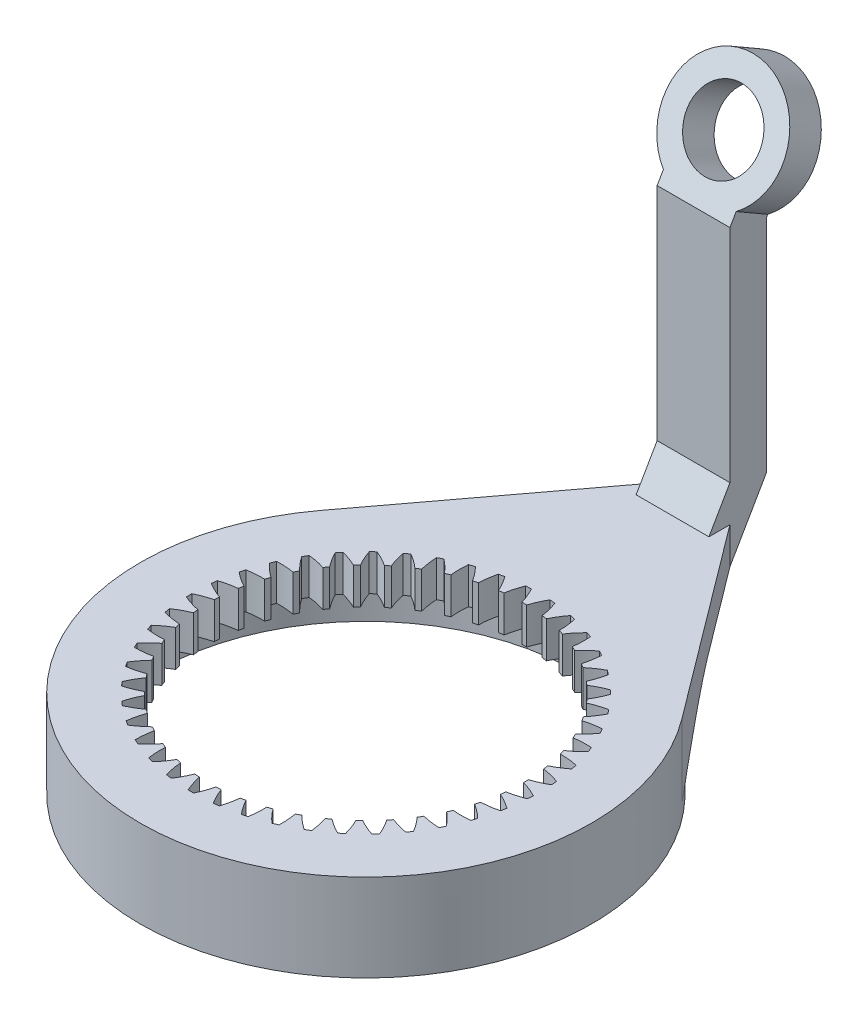
SolidWorks part; units mm, degrees
ref_plane "Front Plane" through (0, 0, 0) normal (0, 0, 1) x (1, 0, 0)
ref_plane "Top Plane" through (0, 0, 0) normal (0, 1, 0) x (1, 0, 0)
ref_plane "Right Plane" through (0, 0, 0) normal (1, 0, 0) x (0, 0, -1)
ref_plane "Plane1" through (0, 5, 0) normal (0, 1, 0) x (1, 0, 0)
sketch "Sketch1" plane through (0, 5, 0) normal (0, 1, 0) x (1, 0, 0)
  circle A0 centre (0, 0) radius 29
  arc A1 (19.702, -8.607) -> (21.3859, -10.3322) centre (12.5395, -17.2823) cw
  arc A2 (21.3859, -10.3322) -> (21.0469, -11.0063) centre (0, 0) cw
  arc A3 (21.0469, -11.0063) -> (18.6579, -10.6834) centre (21.3509, 0.2396) cw
  arc A4 (18.6579, -10.6834) -> (18.3124, -11.2652) centre (0, 0) cw
  arc A5 (18.3124, -11.2652) -> (19.7398, -13.208) centre (10.0122, -18.8593) cw
  arc A6 (19.7398, -13.208) -> (19.3103, -13.8284) centre (0, 0) cw
  arc A7 (19.3103, -13.8284) -> (16.9895, -13.1761) centre (21.1764, -2.7342) cw
  arc A8 (16.9895, -13.1761) -> (16.5664, -13.7042) centre (0, 0) cw
  arc A9 (16.5664, -13.7042) -> (17.7095, -15.8267) centre (7.2901, -20.0692) cw
  arc A10 (17.7095, -15.8267) -> (17.1978, -16.3813) centre (0, 0) cw
  arc A11 (17.1978, -16.3813) -> (14.9904, -15.4123) centre (20.5898, -5.6548) cw
  arc A12 (14.9904, -15.4123) -> (14.4979, -15.8764) centre (0, 0) cw
  arc A13 (14.4979, -15.8764) -> (15.3345, -18.1374) centre (4.426, -20.8884) cw
  arc A14 (15.3345, -18.1374) -> (14.7506, -18.6153) centre (0, 0) cw
  arc A15 (14.7506, -18.6153) -> (12.6995, -17.3486) centre (19.6024, -8.4653) cw
  arc A16 (12.6995, -17.3486) -> (12.1472, -17.7396) centre (0, 0) cw
  arc A17 (12.1472, -17.7396) -> (12.661, -20.095) centre (1.4758, -21.3011) cw
  arc A18 (12.661, -20.095) -> (12.0163, -20.487) centre (0, 0) cw
  arc A19 (12.0163, -20.487) -> (10.1614, -18.9472) centre (18.2335, -11.1111) cw
  arc A20 (10.1614, -18.9472) -> (9.5601, -19.2576) centre (0, 0) cw
  arc A21 (9.5601, -19.2576) -> (9.7411, -21.6615) centre (-1.5031, -21.2992) cw
  arc A22 (9.7411, -21.6615) -> (9.0481, -21.96) centre (0, 0) cw
  arc A23 (9.0481, -21.96) -> (7.4256, -20.177) centre (16.5097, -13.5405) cw
  arc A24 (7.4256, -20.177) -> (6.787, -20.4007) centre (0, 0) cw
  arc A25 (6.787, -20.4007) -> (6.6316, -22.8064) centre (-4.4527, -20.8828) cw
  arc A26 (6.6316, -22.8064) -> (5.9038, -23.0055) centre (0, 0) cw
  arc A27 (5.9038, -23.0055) -> (4.5453, -21.0141) centre (14.4645, -15.7065) cw
  arc A28 (4.5453, -21.0141) -> (3.8817, -21.1467) centre (0, 0) cw
  arc A29 (3.8817, -21.1467) -> (3.393, -23.5074) centre (-7.3157, -20.0598) cw
  arc A30 (3.393, -23.5074) -> (2.6446, -23.6033) centre (0, 0) cw
  arc A31 (2.6446, -23.6033) -> (1.5764, -21.4421) centre (12.1379, -17.5667) cw
  arc A32 (1.5764, -21.4421) -> (0.9009, -21.4811) centre (0, 0) cw
  arc A33 (0.9009, -21.4811) -> (0.0884, -23.7508) centre (-10.0363, -18.8465) cw
  arc A34 (0.0884, -23.7508) -> (-0.6661, -23.7417) centre (0, 0) cw
  arc A35 (-0.6661, -23.7417) -> (-1.4231, -21.4529) centre (9.5749, -19.085) cw
  arc A36 (-1.4231, -21.4529) -> (-2.0975, -21.3974) centre (0, 0) cw
  arc A37 (-2.0975, -21.3974) -> (-3.2179, -23.532) centre (-12.5615, -17.2663) cw
  arc A38 (-3.2179, -23.532) -> (-3.9638, -23.4179) centre (0, 0) cw
  arc A39 (-3.9638, -23.4179) -> (-4.3949, -21.046) centre (6.8256, -20.2318) cw
  arc A40 (-4.3949, -21.046) -> (-5.055, -20.8973) centre (0, 0) cw
  arc A41 (-5.055, -20.8973) -> (-6.4616, -22.8551) centre (-14.8423, -15.35) cw
  arc A42 (-6.4616, -22.8551) -> (-7.1844, -22.6384) centre (0, 0) cw
  arc A43 (-7.1844, -22.6384) -> (-7.2811, -20.2296) centre (3.9435, -20.9849) cw
  arc A44 (-7.2811, -20.2296) -> (-7.9142, -19.9904) centre (0, 0) cw
  arc A45 (-7.9142, -19.9904) -> (-9.5796, -21.7334) centre (-16.8342, -13.135) cw
  arc A46 (-9.5796, -21.7334) -> (-10.2651, -21.4182) centre (0, 0) cw
  arc A47 (-10.2651, -21.4182) -> (-10.0257, -19.0193) centre (0.9846, -21.3295) cw
  arc A48 (-10.0257, -19.0193) -> (-10.6193, -18.6944) centre (0, 0) cw
  arc A49 (-10.6193, -18.6944) -> (-12.511, -20.1887) centre (-18.4984, -10.6643) cw
  arc A50 (-12.511, -20.1887) -> (-13.146, -19.7811) centre (0, 0) cw
  arc A51 (-13.146, -19.7811) -> (-12.5751, -17.4389) centre (-1.9935, -21.2589) cw
  arc A52 (-12.5751, -17.4389) -> (-13.1177, -17.0345) centre (0, 0) cw
  arc A53 (-13.1177, -17.0345) -> (-15.199, -18.251) centre (-19.8025, -7.986) cw
  arc A54 (-15.199, -18.251) -> (-15.7711, -17.759) centre (0, 0) cw
  arc A55 (-15.7711, -17.759) -> (-14.8798, -15.5191) centre (-4.9328, -20.7746) cw
  arc A56 (-14.8798, -15.5191) -> (-15.3608, -15.0431) centre (0, 0) cw
  arc A57 (-15.3608, -15.0431) -> (-17.5912, -15.9581) centre (-20.7212, -5.1523) cw
  arc A58 (-17.5912, -15.9581) -> (-18.0892, -15.3913) centre (0, 0) cw
  arc A59 (-18.0892, -15.3913) -> (-16.8948, -13.2972) centre (-7.776, -19.8859) cw
  arc A60 (-16.8948, -13.2972) -> (-17.3049, -12.7589) centre (0, 0) cw
  arc A61 (-17.3049, -12.7589) -> (-19.6409, -13.3546) centre (-21.2367, -2.2183) cw
  arc A62 (-19.6409, -13.3546) -> (-20.0552, -12.724) centre (0, 0) cw
  arc A63 (-20.0552, -12.724) -> (-18.581, -10.8165) centre (-10.468, -18.6102) cw
  arc A64 (-18.581, -10.8165) -> (-18.9122, -10.2264) centre (0, 0) cw
  arc A65 (-18.9122, -10.2264) -> (-21.3084, -10.4911) centre (-21.3387, 0.7588) cw
  arc A66 (-21.3084, -10.4911) -> (-21.6309, -9.809) centre (0, 0) cw
  arc A67 (-21.6309, -9.809) -> (-19.9055, -8.1253) centre (-12.9561, -16.9722) cw
  arc A68 (-19.9055, -8.1253) -> (-20.1514, -7.4948) centre (0, 0) cw
  arc A69 (-20.1514, -7.4948) -> (-22.5611, -7.4235) centre (-21.0254, 3.7212) cw
  arc A70 (-22.5611, -7.4235) -> (-22.7855, -6.7031) centre (0, 0) cw
  arc A71 (-22.7855, -6.7031) -> (-20.8426, -5.2759) centre (-15.1921, -15.0039) cw
  arc A72 (-20.8426, -5.2759) -> (-20.9983, -4.6173) centre (0, 0) cw
  arc A73 (-20.9983, -4.6173) -> (-23.3747, -4.2114) centre (-20.3029, 6.6112) cw
  arc A74 (-23.3747, -4.2114) -> (-23.4966, -3.4667) centre (0, 0) cw
  arc A75 (-23.4966, -3.4667) -> (-21.374, -2.3238) centre (-17.1324, -12.7435) cw
  arc A76 (-21.374, -2.3238) -> (-21.4366, -1.65) centre (0, 0) cw
  arc A77 (-21.4366, -1.65) -> (-23.7333, -0.9173) centre (-19.1852, 9.3724) cw
  arc A78 (-23.7333, -0.9173) -> (-23.7504, -0.1629) centre (0, 0) cw
  arc A79 (-23.7504, -0.1629) -> (-21.4894, 0.6735) centre (-18.7392, -10.2351) cw
  arc A80 (-21.4894, 0.6735) -> (-21.4576, 1.3495) centre (0, 0) cw
  arc A81 (-21.4576, 1.3495) -> (-23.63, 2.3947) centre (-17.6941, 11.9513) cw
  arc A82 (-23.63, 2.3947) -> (-23.542, 3.1441) centre (0, 0) cw
  arc A83 (-23.542, 3.1441) -> (-21.1866, 3.6577) centre (-19.9813, -7.5275) cw
  arc A84 (-21.1866, 3.6577) -> (-21.061, 4.3227) centre (0, 0) cw
  arc A85 (-21.061, 4.3227) -> (-23.0667, 5.6601) centre (-15.8586, 14.2975) cw
  arc A86 (-23.0667, 5.6601) -> (-22.8753, 6.3899) centre (0, 0) cw
  arc A87 (-22.8753, 6.3899) -> (-20.4713, 6.5707) centre (-20.8345, -4.6734) cw
  arc A88 (-20.4713, 6.5707) -> (-20.2544, 7.2117) centre (0, 0) cw
  arc A89 (-20.2544, 7.2117) -> (-22.0545, 8.8152) centre (-13.7145, 16.3655) cw
  arc A90 (-22.0545, 8.8152) -> (-21.7634, 9.5114) centre (0, 0) cw
  arc A91 (-21.7634, 9.5114) -> (-19.3576, 9.3558) centre (-21.2821, -1.7283) cw
  arc A92 (-19.3576, 9.3558) -> (-19.0536, 9.9604) centre (0, 0) cw
  arc A93 (-19.0536, 9.9604) -> (-20.613, 11.7988) centre (-11.3034, 18.1149) cw
  arc A94 (-20.613, 11.7988) -> (-20.2278, 12.4477) centre (0, 0) cw
  arc A95 (-20.2278, 12.4477) -> (-17.8672, 11.9588) centre (-21.3156, 1.2504) cw
  arc A96 (-17.8672, 11.9588) -> (-17.482, 12.5152) centre (0, 0) cw
  arc A97 (-17.482, 12.5152) -> (-18.7703, 14.5528) centre (-8.6723, 19.5117) cw
  arc A98 (-18.7703, 14.5528) -> (-18.2986, 15.1417) centre (0, 0) cw
  arc A99 (-18.2986, 15.1417) -> (-16.0289, 14.3291) centre (-20.9341, 4.2048) cw
  arc A100 (-16.0289, 14.3291) -> (-15.5701, 14.8264) centre (0, 0) cw
  arc A101 (-15.5701, 14.8264) -> (-16.5623, 17.0235) centre (-5.8724, 20.5288) cw
  arc A102 (-16.5623, 17.0235) -> (-16.0132, 17.541) centre (0, 0) cw
  arc A103 (-16.0132, 17.541) -> (-13.8787, 16.4204) centre (-20.1452, 7.0773) cw
  arc A104 (-13.8787, 16.4204) -> (-13.3551, 16.8491) centre (0, 0) cw
  arc A105 (-13.3551, 16.8491) -> (-14.0319, 19.1629) centre (-2.9581, 21.1463) cw
  arc A106 (-14.0319, 19.1629) -> (-13.4161, 19.5989) centre (0, 0) cw
  arc A107 (-13.4161, 19.5989) -> (-11.4584, 18.1922) centre (-18.9642, 9.8121) cw
  arc A108 (-11.4584, 18.1922) -> (-10.8802, 18.5438) centre (0, 0) cw
  arc A109 (-10.8802, 18.5438) -> (-11.2284, 20.9292) centre (0.0136, 21.3522) cw
  arc A110 (-11.2284, 20.9292) -> (-10.5579, 21.2753) centre (0, 0) cw
  arc A111 (-10.5579, 21.2753) -> (-8.815, 19.6098) centre (-17.414, 12.3559) cw
  arc A112 (-8.815, 19.6098) -> (-8.1935, 19.8775) centre (0, 0) cw
  arc A113 (-8.1935, 19.8775) -> (-8.2063, 22.2882) centre (2.9852, 21.1425) cw
  arc A114 (-8.2063, 22.2882) -> (-7.4942, 22.5377) centre (0, 0) cw
  arc A115 (-7.4942, 22.5377) -> (-6.0001, 20.6458) centre (-15.5249, 14.6592) cw
  arc A116 (-6.0001, 20.6458) -> (-5.3473, 20.8244) centre (0, 0) cw
  arc A117 (-5.3473, 20.8244) -> (-5.0246, 23.2134) centre (5.8986, 20.5213) cw
  arc A118 (-5.0246, 23.2134) -> (-4.2846, 23.3613) centre (0, 0) cw
  arc A119 (-4.2846, 23.3613) -> (-3.0683, 21.2799) centre (-13.3337, 16.6772) cw
  arc A120 (-3.0683, 21.2799) -> (-2.3971, 21.366) centre (0, 0) cw
  arc A121 (-2.3971, 21.366) -> (-1.745, 23.6868) centre (8.6972, 19.5007) cw
  arc A122 (-1.745, 23.6868) -> (-0.9917, 23.7303) centre (0, 0) cw
  arc A123 (-0.9917, 23.7303) -> (-0.0769, 21.4999) centre (-10.8829, 18.3706) cw
  arc A124 (-0.0769, 21.4999) -> (0.5998, 21.4916) centre (0, 0) cw
  arc A125 (0.5998, 21.4916) -> (1.5686, 23.6991) centre (11.3265, 18.1005) cw
  arc A126 (1.5686, 23.6991) -> (2.3206, 23.6374) centre (0, 0) cw
  arc A127 (2.3206, 23.6374) -> (2.9161, 21.3013) centre (-8.2203, 19.7064) cw
  arc A128 (2.9161, 21.3013) -> (3.585, 21.199) centre (0, 0) cw
  arc A129 (3.585, 21.199) -> (4.8516, 23.2502) centre (13.7354, 16.348) cw
  arc A130 (4.8516, 23.2502) -> (5.5877, 23.0844) centre (0, 0) cw
  arc A131 (5.5877, 23.0844) -> (5.8523, 20.6882) centre (-5.3977, 20.6587) cw
  arc A132 (5.8523, 20.6882) -> (6.5005, 20.4938) centre (0, 0) cw
  arc A133 (6.5005, 20.4938) -> (8.0402, 22.3487) centre (15.8769, 14.2773) cw
  arc A134 (8.0402, 22.3487) -> (8.746, 22.082) centre (0, 0) cw
  arc A135 (8.746, 22.082) -> (8.6746, 19.6724) centre (-2.47, 21.2089) cw
  arc A136 (8.6746, 19.6724) -> (9.2894, 19.3896) centre (0, 0) cw
  arc A137 (9.2894, 19.3896) -> (11.0723, 21.0123) centre (17.7094, 11.9287) cw
  arc A138 (11.0723, 21.0123) -> (11.7341, 20.6499) centre (0, 0) cw
  arc A139 (11.7341, 20.6499) -> (11.328, 18.2737) centre (0.5057, 21.3462) cw
  arc A140 (11.328, 18.2737) -> (11.8975, 17.9081) centre (0, 0) cw
  arc A141 (11.8975, 17.9081) -> (13.8889, 19.2668) centre (19.1972, 9.3479) cw
  arc A142 (13.8889, 19.2668) -> (14.4939, 18.8159) centre (0, 0) cw
  arc A143 (14.4939, 18.8159) -> (13.761, 16.5193) centre (3.4716, 21.0681) cw
  arc A144 (13.761, 16.5193) -> (14.274, 16.078) centre (0, 0) cw
  arc A145 (14.274, 16.078) -> (16.4351, 17.1463) centre (20.3114, 6.5852) cw
  arc A146 (16.4351, 17.1463) -> (16.9715, 16.6156) centre (0, 0) cw
  arc A147 (16.9715, 16.6156) -> (15.9261, 14.4433) centre (6.3699, 20.3799) cw
  arc A148 (15.9261, 14.4433) -> (16.3727, 13.935) centre (0, 0) cw
  arc A149 (16.3727, 13.935) -> (18.6615, 14.6921) centre (21.0302, 3.6943) cw
  arc A150 (18.6615, 14.6921) -> (19.1188, 14.0919) centre (0, 0) cw
  arc A151 (19.1188, 14.0919) -> (17.7812, 12.0863) centre (9.1443, 19.295) cw
  arc A152 (17.7812, 12.0863) -> (18.1528, 11.5207) centre (0, 0) cw
  arc A153 (18.1528, 11.5207) -> (20.5246, 11.952) centre (21.3397, 0.7315) cw
  arc A154 (20.5246, 11.952) -> (20.8939, 11.294) centre (0, 0) cw
  arc A155 (20.8939, 11.294) -> (19.2902, 9.494) centre (11.7406, 17.8346) cw
  arc A156 (19.2902, 9.494) -> (19.5795, 8.8822) centre (0, 0) cw
  arc A157 (19.5795, 8.8822) -> (21.9883, 8.9792) centre (21.2338, -2.2455) cw
  arc A158 (21.9883, 8.9792) -> (22.2624, 8.2762) centre (0, 0) cw
  arc A159 (22.2624, 8.2762) -> (20.4238, 6.7169) centre (14.1085, 16.0271) cw
  arc A160 (20.4238, 6.7169) -> (20.6251, 6.0708) centre (0, 0) cw
  arc A161 (20.6251, 6.0708) -> (23.0239, 5.8316) centre (20.7146, -5.1788) cw
  arc A162 (23.0239, 5.8316) -> (23.1976, 5.0973) centre (0, 0) cw
  arc A163 (23.1976, 5.0973) -> (21.1599, 3.8091) centre (16.2017, 13.9076) cw
  arc A164 (21.1599, 3.8091) -> (21.2693, 3.1413) centre (0, 0) cw
  arc A165 (21.2693, 3.1413) -> (23.6115, 2.5706) centre (19.7923, -8.0113) cw
  arc A166 (23.6115, 2.5706) -> (23.6812, 1.8192) centre (0, 0) cw
  arc A167 (23.6812, 1.8192) -> (21.4841, 0.8272) centre (17.9796, 11.5174) cw
  arc A168 (21.4841, 0.8272) -> (21.4995, 0.1506) centre (0, 0) cw
  arc A169 (21.4995, 0.1506) -> (23.7395, -0.7405) centre (18.4847, -10.6879) cw
  arc A170 (23.7395, -0.7405) -> (23.7039, -1.4942) centre (0, 0) cw
  arc A171 (23.7039, -1.4942) -> (21.3901, -2.1709) centre (19.4075, 8.903) cw
  arc A172 (21.3901, -2.1709) -> (21.3112, -2.843) centre (0, 0) cw
  arc A173 (21.3112, -2.843) -> (23.4054, -4.0372) centre (16.8174, -13.1565) cw
  arc A174 (23.4054, -4.0372) -> (23.2653, -4.7787) centre (0, 0) cw
  arc A175 (23.2653, -4.7787) -> (20.8798, -5.1267) centre (20.4577, 6.1154) cw
  arc A176 (20.8798, -5.1267) -> (20.7081, -5.7813) centre (0, 0) cw
  arc A177 (20.7081, -5.7813) -> (22.6157, -7.2553) centre (14.8227, -15.369) cw
  arc A178 (22.6157, -7.2553) -> (22.3738, -7.9701) centre (0, 0) cw
  arc A179 (22.3738, -7.9701) -> (19.9631, -7.9827) centre (21.1097, 3.2087) cw
  arc A180 (19.9631, -7.9827) -> (19.702, -8.607) centre (0, 0) cw
extrude "Boss-Extrude1" add sketch "Sketch1" against normal blind 5
sketch "Sketch2" plane through (0, 5, 0) normal (0, 1, 0) x (1, 0, 0)
  circle A0 centre (0, 0) radius 31
  circle A1 centre (0, 0) radius 29 construction
  circle A2 centre (0, 0) radius 29
  dimension "D1" = 62
extrude "Boss-Extrude2" add sketch "Sketch2" against normal blind 12
sketch "Sketch3" plane through (0, 5, 0) normal (0, 1, 0) x (1, 0, 0)
  line L0 (0, 0) -> (0, 45) construction
  line L1 (-5, 45) -> (5, 45)
  line L2 (-5, 45) -> (-24.8, 18.6)
  line L3 (5, 45) -> (24.8, 18.6)
  circle A0 centre (0, 0) radius 31 construction
  circle A1 centre (0, 0) radius 31
  dimension "D1" = 45
  dimension "D2" = 10
  dimension "D3" = 5
extrude "Boss-Extrude3" add sketch "Sketch3" against normal blind 5 contours A1 L0 L1 L2 | L0 A1 L3 L1 region at (-7.2647, 5, -35.1643) region at (7.2647, 5, -35.1643)
fillet "Fillet1" radius 5 1 edges at (0, 0, -31)
sketch "Sketch4" plane through (0, 0, 0) normal (1, 0, 0) x (0, 0, -1)
  line L0 (45, 0) -> (42.1132, 5)
  line L1 (45, 5) -> (18.6, 5) construction
  line L5 (45, 0) -> (33.2424, 0) construction
  line L6 (45, 0) -> (50, 8.6603)
  line L7 (42.1132, 5) -> (45, 10)
  line L9 (50, 8.6603) -> (50, 39)
  line L10 (45, 10) -> (45, 40.3397)
  line L12 (-31, -7) -> (31, -7) construction
  line L13 (50, 39) -> (57.5, 51.9904)
  line L14 (45, 40.3397) -> (53.1699, 54.4904)
  line L15 (57.5, 51.9904) -> (53.1699, 54.4904)
  dimension "D1" = 60
  dimension "D2" = 60
  dimension "D3" = 10
  dimension "D4" = 34
  dimension "D5" = 12
  dimension "D6" = 15
  dimension "D7" = 5
  dimension "D8" = 5
extrude "Boss-Extrude4" add sketch "Sketch4" against normal up to vertex (5 mm away) and the other way up to vertex (5 mm away) up to point (-5, 0, -45) other way up to point (5, 0, -45)
sketch "Sketch5" plane through (0, -9.4006, -16.2824) normal (0, 0.5, 0.866) x (1, 0, 0)
  line L0 (0, 57.4352) -> (0, 73.775) construction
  line L1 (-5, 57.4352) -> (5, 57.4352) construction
  line L2 (-5, 73.775) -> (5, 73.775) construction
  line L7 (-5, 57.4352) -> (5, 57.4352)
  line L8 (5, 57.4352) -> (5, 73.775)
  line L9 (5, 73.775) -> (-5, 73.775)
  line L10 (-5, 73.775) -> (-5, 57.4352)
  line L11 (-5, 57.4352) -> (5, 57.4352)
  line L12 (5, 57.4352) -> (5, 73.775)
  line L13 (5, 73.775) -> (-5, 73.775)
  line L14 (-5, 73.775) -> (-5, 57.4352)
  circle A0 centre (0, 65.6051) radius 8.1699
  dimension "D1" = 16.3397
  dimension "D2" = 0
extrude "Boss-Extrude5" add sketch "Sketch5" against normal up to surface (5 mm away) contours L14 A0 | L12 A0 region at (-6.2917, 47.4151, -49.0849) region at (6.2917, 47.4151, -49.0849) up to face at (0, 45.4952, -53.75)
sketch "Sketch6" plane through (0, -9.4006, -16.2824) normal (0, 0.5, 0.866) x (1, 0, 0)
  line L6 (-5, 57.4352) -> (5, 57.4352)
  line L7 (5, 57.4352) -> (5, 59.1439)
  line L8 (5, 72.0663) -> (5, 73.775)
  line L9 (5, 73.775) -> (-5, 73.775)
  line L10 (-5, 73.775) -> (-5, 72.0663)
  line L11 (-5, 59.1439) -> (-5, 57.4352)
  line L14 (5, 72.0663) -> (5, 73.775)
  line L15 (5, 73.775) -> (-5, 73.775)
  line L16 (-5, 73.775) -> (-5, 72.0663)
  circle A1 centre (0, 65.6051) radius 5
  arc A2 (5, 59.1439) -> (5, 72.0663) centre (0, 65.6051) ccw
  arc A3 (-5, 72.0663) -> (-5, 59.1439) centre (0, 65.6051) ccw
  arc A6 (5, 72.0663) -> (-5, 72.0663) centre (0, 65.6051) ccw
  line M14 (5, 72.0663) -> (5, 73.775)
  line M15 (5, 73.775) -> (-5, 73.775)
  line M16 (-5, 73.775) -> (-5, 72.0663)
  dimension "D2" = 10
  dimension "D1" = 0
extrude "Cut-Extrude1" cut sketch "Sketch6" against normal through all contours A6 L15 M16 | A6 M14 M15 | A1 region at (-3.7777, 54.0557, -52.9189) region at (3.7777, 54.0557, -52.9189) region at (0, 47.4151, -49.0849)
